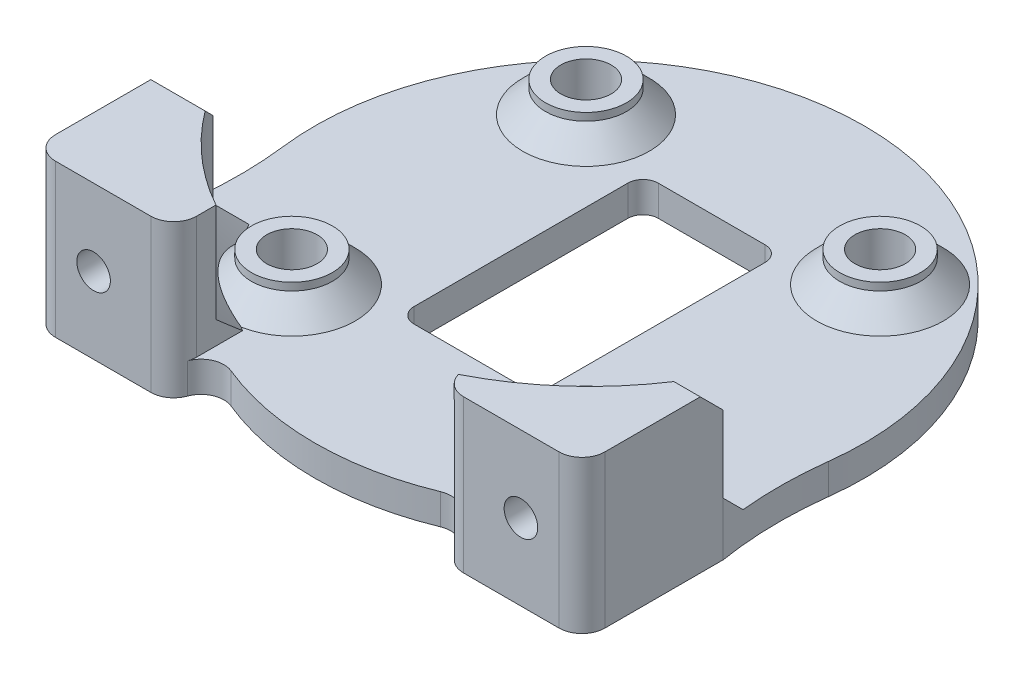
SolidWorks part; units mm, degrees
material "PETG"
ref_plane "Płaszczyzna przednia" through (0, 0, 0) normal (0, 0, 1) x (1, 0, 0)
ref_plane "Płaszczyzna górna" through (0, 0, 0) normal (0, 1, 0) x (1, 0, 0)
ref_plane "Płaszczyzna prawa" through (0, 0, 0) normal (1, 0, 0) x (0, 0, -1)
sketch "Sketch1" plane through (0, 0, 0) normal (0, 1, 0) x (1, 0, 0)
  circle A0 centre (0, 0) radius 36
  dimension "D1" = 72
extrude "Boss-Extrude1" add sketch "Sketch1" along normal blind 4
hole_wizard "Ø6.6 (6.6) Diameter Hole1" positions "Sketch2" profile "Sketch3" hole size "Ø6.6" standard "DIN" end condition up to next
sketch "Sketch2" plane through (0, 4, 0) normal (0, 1, 0) x (1, 0, 0)
  line L1 (19.0323, 19.0293) -> (-19.5051, 19.0293)
  point P0 (-19.5051, 19.0293)
  point P10 (19.0323, 19.0293)
  point P11 (19.0323, -19.508)
  point P12 (-19.5051, -19.508)
  dimension "D1" = 27.25
  dimension "D2" = 4
sketch "Sketch3" plane through (-19.5051, 4, -19.0293) normal (1, 0, 0) x (0, 0, 1)
  line L0 (0, 0) -> (0, 4)
  line L1 (0, 4) -> (3.3, 4)
  line L2 (3.3, 4) -> (3.3, 0)
  line L5 (3.3, 0) -> (0, 0)
  line L11 (0, -6.35) -> (0, 107.95) construction
  dimension "Thru Hole Dia." = 6.6
  dimension "Thru Hole Depth" = 4
sketch "Sketch4" plane through (0, 4, 0) normal (0, 1, 0) x (1, 0, 0)
  circle A0 centre (-19.5051, -19.508) radius 3.3 construction
  circle A1 centre (19.0323, -19.508) radius 3.3 construction
  circle A2 centre (19.0323, 19.0293) radius 3.3 construction
  circle A3 centre (-19.5051, 19.0293) radius 3.3 construction
  circle A4 centre (-19.5051, -19.508) radius 3.3
  circle A5 centre (19.0323, -19.508) radius 3.3
  circle A6 centre (19.0323, 19.0293) radius 3.3
  circle A7 centre (-19.5051, 19.0293) radius 3.3
  circle A8 centre (-19.5051, 19.0293) radius 5.3
  circle A9 centre (19.0323, 19.0293) radius 5.3
  circle A10 centre (19.0323, -19.508) radius 5.3
  circle A11 centre (-19.5051, -19.508) radius 5.3
  dimension "D1" = 2
extrude "Boss-Extrude2" add sketch "Sketch4" along normal blind 4
sketch "Sketch5" plane through (0, 0, 0) normal (0, -1, 0) x (1, 0, 0)
  line L0 (-36, 18.5) -> (-36, 37)
  line L1 (36, 37) -> (17.5, 37)
  line L2 (36, 37) -> (36, 18.5)
  line L3 (36, 18.5) -> (30.8828, 18.5)
  line L4 (-30.8828, 18.5) -> (-36, 18.5)
  line L5 (-36, 31.9282) -> (-17.5, 31.9282) construction
  line L7 (-17.5, 37) -> (-17.5, 31.4603)
  line L9 (17.5, 37) -> (17.5, 31.4603)
  line L10 (17.5, 31.7771) -> (36, 31.7771) construction
  line L11 (-17.5, 37) -> (-36, 37)
  circle A0 centre (0, 0) radius 36 construction
  arc A1 (30.8828, 18.5) -> (17.5, 31.4603) centre (0, 0) ccw
  arc A2 (-17.5, 31.4603) -> (-30.8828, 18.5) centre (0, 0) ccw
  dimension "D1" = 72
  dimension "D2" = 35
extrude "Boss-Extrude3" add sketch "Sketch5" against normal blind 20
sketch "Sketch6" plane through (0, 0, 37) normal (0, 0, 1) x (1, 0, 0)
  line L0 (-28, 0) -> (-28, 10) construction
  line L1 (36, 0) -> (17.5, 0) construction
  line L2 (-28, 10) -> (-28, 20) construction
  line L3 (36, 20) -> (17.5, 20) construction
  line L4 (-36, 20) -> (-36, 0) construction
  line L5 (0, 0) -> (0, 66.4193) construction
  circle A0 centre (-28, 10) radius 2.2
  circle A2 centre (28, 10) radius 2.2
  dimension "D1" = 8
  dimension "D2" = 4.4
extrude "Cut-Extrude1" cut sketch "Sketch6" against normal blind 8
fillet "Fillet1" radius 50 2 edges at (30.8828, 2, 18.5) (-30.8828, 2, 18.5)
fillet "Fillet2" radius 3 4 edges at (36, 10, 37) (17.5, 10, 37) (-17.5, 10, 37) (-36, 10, 37)
chamfer "Chamfer1" distance 3 angle 45 11 edges at (-19.5051, 4, 24.808) (19.0323, 4, 24.808) (19.0323, 4, -13.7293) (-19.5051, 4, -13.7293) (33.4414, 4, 18.5) (-33.4414, 4, 18.5) (25.0443, 4, 25.8608) (-33.4414, 20, 18.5) (25.0443, 20, 25.8608) (33.4414, 20, 18.5) (-25.0443, 4, 25.8608)
fillet "Fillet4" radius 3 2 edges at (17.5, 2, 31.4603) (-17.5, 2, 31.4603)
sketch "Sketch7" plane through (0, 4, 0) normal (0, 1, 0) x (1, 0, 0)
  line L1 (-9, -16) -> (9, -16)
  line L2 (-9, -16) -> (-9, 16)
  line L3 (-9, 16) -> (9, 16)
  line L4 (9, -16) -> (9, 16)
  line L5 (-9, -16) -> (9, 16) construction
  line L6 (-9, 16) -> (9, -16) construction
  point P0 (0, 0)
  dimension "D1" = 32
  dimension "D2" = 18
extrude "Cut-Extrude2" cut sketch "Sketch7" against normal through all and the other way through all
fillet "Fillet5" radius 2 4 edges at (-9, 2, 16) (9, 2, 16) (9, 2, -16) (-9, 2, -16)
